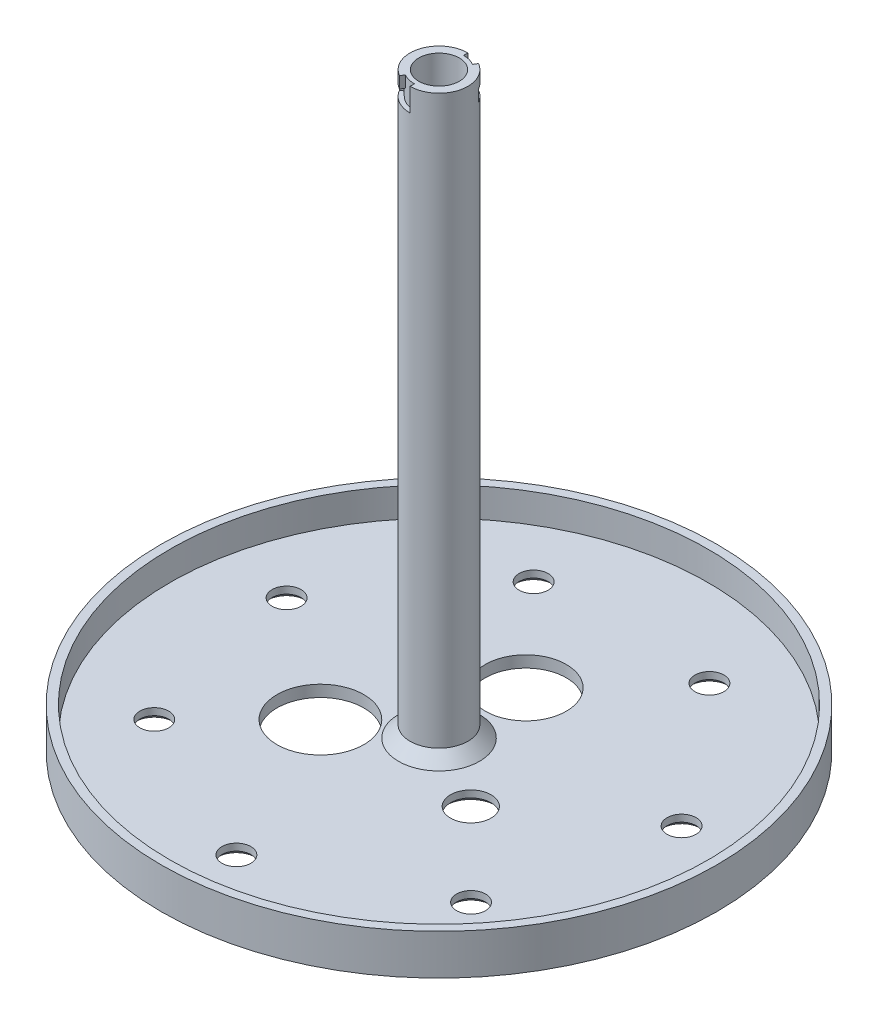
SolidWorks part; units mm, degrees
ref_plane "Front Plane" through (0, 0, 0) normal (0, 0, 1) x (1, 0, 0)
ref_plane "Top Plane" through (0, 0, 0) normal (0, 1, 0) x (1, 0, 0)
ref_plane "Right Plane" through (0, 0, 0) normal (1, 0, 0) x (0, 0, -1)
sketch "Sketch1" plane through (0, 0, 0) normal (0, 1, 0) x (1, 0, 0)
  line L0 (0, 15) -> (0, 0) construction
  line L1 (0, 0) -> (-12.9904, -7.5) construction
  line L2 (0, 0) -> (12.9904, -7.5) construction
  circle A0 centre (0, 0) radius 46.5
  circle A1 centre (0, 15) radius 7
  circle A2 centre (-12.9904, -7.5) radius 7.5
  circle A3 centre (12.9904, -7.5) radius 3.5
  circle A4 centre (0, 0) radius 3.5
  point P3 (0, 15)
  point P8 (12.9904, -7.5)
  point P9 (-12.9904, -7.5)
  point P10 (0, 0)
  dimension "D1" = 93
  dimension "D4" = 14
  dimension "D5" = 15
  dimension "D6" = 7
  dimension "D7" = 7
  dimension "D2" = 15
  dimension "D3" = 3
extrude "Boss-Extrude1" add sketch "Sketch1" along normal blind 2
sketch "Sketch2" plane through (0, 2, 0) normal (0, 1, 0) x (1, 0, 0)
  line L0 (0, 0) -> (12.9904, -7.5) construction
  line L1 (0, 0) -> (0, 46.5) construction
  line L2 (0, 0) -> (-12.9904, -7.5) construction
  line L3 (0, 0) -> (-40.2702, -23.25) construction
  line L4 (0, 0) -> (40.2702, -23.25) construction
  circle A0 centre (0, 0) radius 46.5 construction
  circle A1 centre (-12.9904, -7.5) radius 7.5 construction
  circle A2 centre (12.9904, -7.5) radius 3.5 construction
  circle A3 centre (0, 0) radius 25
  circle A4 centre (21.6506, -12.5) radius 3
  circle A5 centre (-21.6506, -12.5) radius 3
  circle A6 centre (0, 25) radius 3
  point P22 (0, 0)
  dimension "D1" = 50
  dimension "D2" = 6
  dimension "D3" = 3
ref_plane "Plane1" through (0, 0, 0) normal (-0.5, 0, -0.866) x (-0.866, 0, 0.5)
sketch "Sketch3" plane through (0, 2, 0) normal (0, 1, 0) x (1, 0, 0)
  circle A0 centre (0, 0) radius 3.5
  circle A1 centre (0, 0) radius 5
  dimension "D1" = 10
extrude "Boss-Extrude2" add sketch "Sketch3" along normal blind 100
sketch "Sketch6" plane through (0, 0, 0) normal (0, -1, 0) x (1, 0, 0)
  circle A0 centre (0, 0) radius 35
  circle A1 centre (0, 35) radius 2.5
  circle A2 centre (27.3641, 21.8221) radius 2.5
  circle A3 centre (34.1225, -7.7882) radius 2.5
  circle A4 centre (15.1859, -31.5339) radius 2.5
  circle A5 centre (-15.1859, -31.5339) radius 2.5
  circle A6 centre (-34.1225, -7.7882) radius 2.5
  circle A7 centre (-27.3641, 21.8221) radius 2.5
  point P20 (0, 0)
  dimension "D1" = 70
  dimension "D2" = 5
  dimension "D3" = 7
extrude "Cut-Extrude2" cut sketch "Sketch6" against normal up to next contours A0 A4 | A0 A4 | A0 A3 | A0 A3 | A0 A2 | A0 A2 | A0 A1 | A0 A1 | A0 A7 | A0 A7 | A0 A6 | A0 A6 | A0 A5 | A0 A5 region at (26.5221, 0, 21.1507) region at (28.181, 0, 22.4736) region at (35.1411, 0, -8.0207) region at (33.0725, 0, -7.5486) region at (0, 0, 33.923) region at (0, 0, 36.0448) region at (15.6392, 0, -32.4752) region at (14.7187, 0, -30.5636) region at (-26.5221, 0, 21.1507) region at (-28.181, 0, 22.4736) region at (-15.6392, 0, -32.4752) region at (-14.7187, 0, -30.5636) region at (-33.0725, 0, -7.5486) region at (-35.1411, 0, -8.0207)
chamfer "Chamfer2" distance 0.8 angle 45 8 edges at (0, 0, 32.5) (-27.3641, 0, 19.3221) (-34.1225, 0, -10.2882) (-15.1859, 0, -34.0339) (27.3641, 0, 19.3221) (12.9904, 0, 11) (34.1225, 0, -10.2882) (15.1859, 0, -34.0339)
ref_axis "Axis1" through (0, 102, 0) along (0, -1, 0)
sketch "Sketch7" plane through (0, 0, 0) normal (1, 0, 0) x (0, 0, -1)
  line L1 (5, 102) -> (4.25, 102)
  line L2 (5, 102) -> (5, 100)
  line L3 (5, 100) -> (4.25, 100)
  line L4 (4.25, 102) -> (4.25, 100)
  line L5 (5, 100) -> (4.25, 100)
  line L6 (5, 100) -> (5, 98)
  line L7 (5, 98) -> (4.25, 98)
  line L8 (4.25, 100) -> (4.25, 98)
  dimension "D1" = 2
  dimension "D2" = 0.75
  dimension "D3" = 2
  dimension "D4" = 0.75
revolve "Cut-Revolve1" cut sketch "Sketch7" angle 30 about axis through (0, 102, 0) along (0, -1, 0) region at (0, 101, -4.625)
revolve "Cut-Revolve2" cut sketch "Sketch7<4>" angle 60 about axis through (0, 102, 0) along (0, -1, 0) region at (0, 99, -4.625)
sketch "Sketch7<4>" plane through (0, 0, 0) normal (1, 0, 0) x (0, 0, -1) same geometry as "Sketch7"
pattern_circular "CirPattern5" count 2 over 360 about axis through (0, 102, 0) along (0, -1, 0) of "Cut-Revolve2", "Cut-Revolve1"
sketch "Sketch8" plane through (0, 2, 0) normal (0, 1, 0) x (1, 0, 0)
  circle A0 centre (0, 0) radius 48
  circle A1 centre (0, 0) radius 46.5
  dimension "D1" = 96
extrude "Boss-Extrude3" add sketch "Sketch8" along normal blind 5 and the other way blind 2 separate body
chamfer "Chamfer3" distance 2 angle 45 1 edges at (0, 2, 5)
